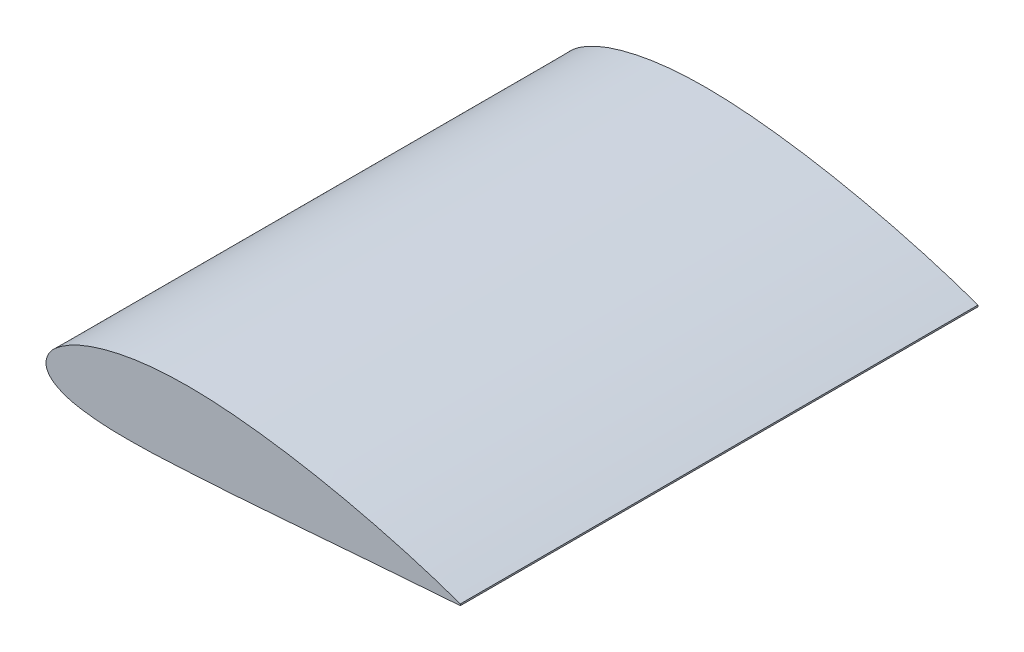
SolidWorks part; units mm, degrees
ref_plane "Front Plane" through (0, 0, 0) normal (0, 0, 1) x (1, 0, 0)
ref_plane "Top Plane" through (0, 0, 0) normal (0, 1, 0) x (1, 0, 0)
ref_plane "Right Plane" through (0, 0, 0) normal (1, 0, 0) x (0, 0, -1)
curve "Curve1"
  spline degree 3 poles (100, 0.19, 0) (98.3361, 0.7648, 0) (95.0209, 1.9101, 0) (88.3728, 3.9912, 0) (80.0503, 6.2751, 0) (70.0446, 8.6136, 0) (60.0387, 10.5135, 0) (50.0311, 11.9338, 0) (40.0203, 12.8297, 0) (31.6571, 12.9227, 0) (24.9839, 12.4514, 0) (19.968, 11.778, 0) (14.9432, 10.7208, 0) (10.7656, 9.4656, 0) (7.4504, 8.0774, 0) (4.9073, 6.7656, 0) (2.7857, 5.314, 0) (0.6786, 3.3349, 0) (-0.6397, 0.4121, 0) (0.9458, -2.0134, 0) (2.8146, -3.2368, 0) (4.9339, -4.1179, 0) (7.4805, -4.6987, 0) (10.818, -5.2015, 0) (14.9919, -5.5599, 0) (20.0003, -5.568, 0) (25.0027, -5.5279, 0) (31.6682, -5.1704, 0) (40.0038, -4.7251, 0) (50.004, -4.0391, 0) (60, -3.2372, 0) (69.9999, -2.4518, 0) (79.9979, -1.6559, 0) (88.3344, -1.0637, 0) (94.9991, -0.5441, 0) (98.3332, -0.308, 0) (100, -0.19, 0) knots 0 0 0 0 0.025365 0.050536 0.100362 0.149678 0.198559 0.247064 0.295267 0.343298 0.367375 0.391611 0.416159 0.441302 0.454325 0.467882 0.482539 0.490995 0.510026 0.521806 0.529148 0.542209 0.554569 0.566721 0.590825 0.614842 0.63886 0.6629 0.711005 0.759146 0.807322 0.855502 0.903677 0.951839 0.975923 1 1 1 1
sketch "Sketch2" plane through (0, 0, 0) normal (0, 0, 1) x (1, 0, 0)
  line L0 (100, 0.19) -> (100, -0.19)
  spline S0 degree 3 poles (938.9809, 1810.8695) (225.0317, -92.4262) (166.4339, -20.4444) (88.3728, 3.9912) (80.0503, 6.2751) (70.0446, 8.6136) (60.0387, 10.5135) (50.0311, 11.9338) (40.0203, 12.8297) (31.6571, 12.9227) (24.9839, 12.4514) (19.968, 11.778) (14.9432, 10.7208) (10.7656, 9.4656) (7.4504, 8.0774) (4.9073, 6.7656) (2.7857, 5.314) (0.6786, 3.3349) (-0.6397, 0.4121) (0.9458, -2.0134) (2.8146, -3.2368) (4.9339, -4.1179) (7.4805, -4.6987) (10.818, -5.2015) (14.9919, -5.5599) (20.0003, -5.568) (25.0027, -5.5279) (31.6682, -5.1704) (40.0038, -4.7251) (50.004, -4.0391) (60, -3.2372) (69.9999, -2.4518) (79.9979, -1.6559) (88.3344, -1.0637) (210.0932, 8.4291) (330.7414, -12.2973) (300.4888, 1979.2297) knots -1.078078 -1.078078 -1.078078 -1.078078 0.025365 0.050536 0.100362 0.149678 0.198559 0.247064 0.295267 0.343298 0.367375 0.391611 0.416159 0.441302 0.454325 0.467882 0.482539 0.490995 0.510026 0.521806 0.529148 0.542209 0.554569 0.566721 0.590825 0.614842 0.63886 0.6629 0.711005 0.759146 0.807322 0.855502 0.903677 0.951839 0.975923 2.663414 2.663414 2.663414 2.663414 only from (100, 0.19) to (100, -0.19) construction
  spline S1 degree 3 poles (100, 0.19) (98.3361, 0.7648) (95.0209, 1.9101) (88.3728, 3.9912) (80.0503, 6.2751) (70.0446, 8.6136) (60.0387, 10.5135) (50.0311, 11.9338) (40.0203, 12.8297) (31.6571, 12.9227) (24.9839, 12.4514) (19.968, 11.778) (14.9432, 10.7208) (10.7656, 9.4656) (7.4504, 8.0774) (4.9073, 6.7656) (2.7857, 5.314) (0.6786, 3.3349) (-0.6397, 0.4121) (0.9458, -2.0134) (2.8146, -3.2368) (4.9339, -4.1179) (7.4805, -4.6987) (10.818, -5.2015) (14.9919, -5.5599) (20.0003, -5.568) (25.0027, -5.5279) (31.6682, -5.1704) (40.0038, -4.7251) (50.004, -4.0391) (60, -3.2372) (69.9999, -2.4518) (79.9979, -1.6559) (88.3344, -1.0637) (94.9991, -0.5441) (98.3332, -0.308) (100, -0.19) knots 0 0 0 0 0.025365 0.050536 0.100362 0.149678 0.198559 0.247064 0.295267 0.343298 0.367375 0.391611 0.416159 0.441302 0.454325 0.467882 0.482539 0.490995 0.510026 0.521806 0.529148 0.542209 0.554569 0.566721 0.590825 0.614842 0.63886 0.6629 0.711005 0.759146 0.807322 0.855502 0.903677 0.951839 0.975923 1 1 1 1
extrude "Boss-Extrude1" add sketch "Sketch2" along normal mid plane 125
ref_plane "base " through (27.5, 0, 0) normal (1, 0, 0) x (0, 0, -1)
sketch "Sketch169" plane through (27.5, 0, 0) normal (1, 0, 0) x (0, 0, -1)
  line L7 (10.5, -0.19) -> (10.5, -23.49)
  line L8 (62.5, -5.5617) -> (62.5, 12.8495) construction
  line L9 (-62.5, -0.19) -> (62.5, -0.19) construction
  line L10 (10.5, -23.49) -> (5.4, -23.49)
  line L11 (5.4, -23.49) -> (5.4, -0.19)
  line L12 (5.4, -0.19) -> (10.5, -0.19)
  dimension "D1" = 52
  dimension "D2" = 5.1
  dimension "D3" = 23.3
extrude "Boss-Extrude7" [suppressed] add sketch "Sketch169" along normal blind 20
sketch "Sketch171" [suppressed] plane through (0, 0, -5.4) normal (0, 0, 1) x (1, 0, 0)
  line L1 (27.5, -49.49) -> (47.5, -49.49)
  line L2 (27.5, -49.49) -> (27.5, -19.49)
  line L3 (27.5, -19.49) -> (47.5, -19.49)
  line L4 (47.5, -49.49) -> (47.5, -19.49)
  line L5 (47.5, -4.2023) -> (47.5, -23.49) construction
  line L6 (27.5, -5.3892) -> (27.5, -23.49) construction
  line L7 (47.5, -23.49) -> (27.5, -23.49) construction
  dimension "D1" = 30
  dimension "D2" = 4
extrude "Boss-Extrude9" [suppressed] add sketch "Sketch171" along normal blind 3
ref_plane "Plane17" [suppressed] through (0, 0, -7.95) normal (0, 0, 1) x (1, 0, 0)
mirror "Mirror4" [suppressed] about plane through (0, 0, -7.95) normal (0, 0, 1)
sketch "Sketch172" [suppressed] plane through (0, 0, -2.4) normal (0, 0, 1) x (1, 0, 0)
  line L0 (27.5, -49.49) -> (47.5, -49.49) construction
  circle A0 centre (37.5, -43.49) radius 2.05
  point P5 (37.5, -49.49)
  dimension "D1" = 4.1
  dimension "D2" = 6
extrude "Cut-Extrude1" [suppressed] cut sketch "Sketch172" against normal through all
ref_axis "Axis1" [suppressed] through (37.5, -43.49, -40.1754) along (0, 0, 1)
